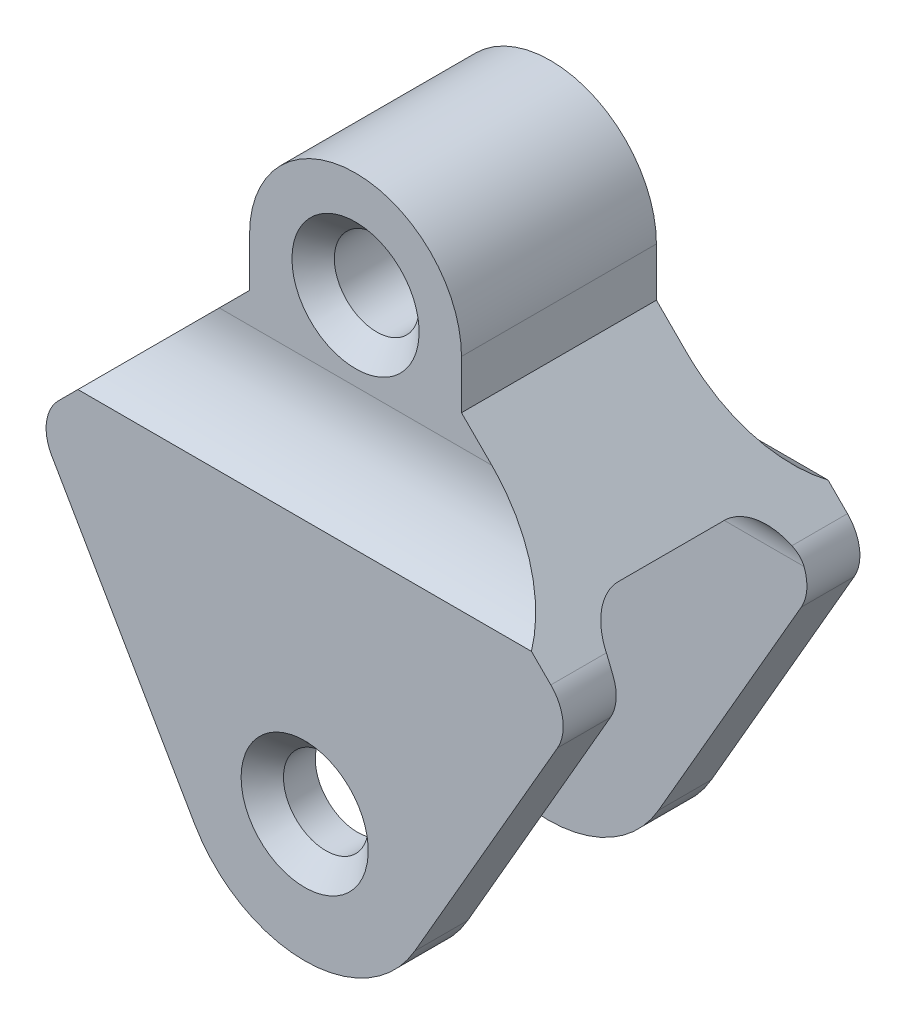
SolidWorks part; units mm, degrees
ref_plane "Front Plane" through (0, 0, 0) normal (0, 0, 1) x (1, 0, 0)
ref_plane "Top Plane" through (0, 0, 0) normal (0, 1, 0) x (1, 0, 0)
ref_plane "Right Plane" through (0, 0, 0) normal (1, 0, 0) x (0, 0, -1)
sketch "Sketch3" plane through (0, 0, 0) normal (0, 0, 1) x (1, 0, 0)
  line L0 (-25, 0) -> (-25, -11.4915)
  line L1 (-25, -11.4915) -> (-63.5085, -50)
  line L2 (-63.5085, -50) -> (-25.9808, -115)
  line L3 (0, 25) -> (0, -137.7863) construction
  line L4 (63.5085, -50) -> (25.9808, -115)
  line L5 (25, -11.4915) -> (63.5085, -50)
  line L6 (25, 0) -> (25, -11.4915)
  circle A0 centre (0, 0) radius 10
  arc A1 (25, 0) -> (-25, 0) centre (0, 0) ccw
  circle A2 centre (0, -100) radius 10
  arc A3 (-25.9808, -115) -> (25.9808, -115) centre (0, -100) ccw
  dimension "D1" = 25
  dimension "D2" = 30
  dimension "D3" = 20
  dimension "D4" = 20
  dimension "D5" = 90
  dimension "D6" = 60
  dimension "D7" = 100
  dimension "D8" = 50
extrude "Boss-Extrude4" add sketch "Sketch3" along normal blind 35
fillet "Fillet3" radius 10 2 edges at (-63.5085, -50, 17.5) (63.5085, -50, 17.5)
sketch "Sketch5" plane through (0, 0, 0) normal (0, 0, -1) x (-1, 0, 0)
  line L0 (-53.5085, -40) -> (53.5085, -40)
  line L1 (-58.0827, -44.5742) -> (-25, -11.4915) construction
  line L2 (25, -11.4915) -> (58.0827, -44.5742) construction
  line L3 (0, 25) -> (-61.5605, 25) construction
  line L4 (-53.5085, -40) -> (-25, -11.4915)
  line L5 (-25, -11.4915) -> (-25, 0)
  line L6 (53.5085, -40) -> (25, -11.4915)
  line L7 (25, -11.4915) -> (25, 0)
  arc A0 (25, 0) -> (-25, 0) centre (0, 0) ccw construction
  arc A1 (25, 0) -> (-25, 0) centre (0, 0) ccw
  dimension "D1" = 65
extrude "Cut-Extrude1" cut sketch "Sketch5" against normal blind 12
sketch "Sketch6" plane through (0, 0, 35) normal (0, 0, 1) x (1, 0, 0)
  line L0 (-51.5085, -38) -> (51.5085, -38)
  line L1 (-25, -11.4915) -> (-58.0827, -44.5742) construction
  line L2 (58.0827, -44.5742) -> (25, -11.4915) construction
  line L3 (0, -130) -> (57.3267, -130) construction
  line L4 (-51.5085, -38) -> (-58.0827, -44.5742)
  line L5 (51.5085, -38) -> (58.0827, -44.5742)
  line L6 (-59.6719, -56.6452) -> (-25.9808, -115)
  line L7 (25.9808, -115) -> (59.6719, -56.6452)
  arc A2 (-25.9808, -115) -> (25.9808, -115) centre (0, -100) ccw construction
  arc A3 (-25.9808, -115) -> (25.9808, -115) centre (0, -100) ccw
  arc A4 (-58.0827, -44.5742) -> (-59.6719, -56.6452) centre (-51.0116, -51.6452) ccw
  arc A5 (58.0827, -44.5742) -> (59.6719, -56.6452) centre (51.0116, -51.6452) cw
  dimension "D1" = 92
extrude "Cut-Extrude2" cut sketch "Sketch6" against normal blind 22.5
fillet "Fillet4" radius 25 1 edges at (0, -40, 12)
fillet "Fillet5" radius 10 1 edges at (0, -38, 12.5)
chamfer "Chamfer2" distance 5 angle 45 1 edges at (-10, 0, 12)
mirror "Mirror2" about plane through (0, -100, 35) normal (0, 0, 1) of bodies 106
chamfer "Chamfer4" distance 5 angle 45 2 edges at (10, -100, 70) (10, -100, 0)
